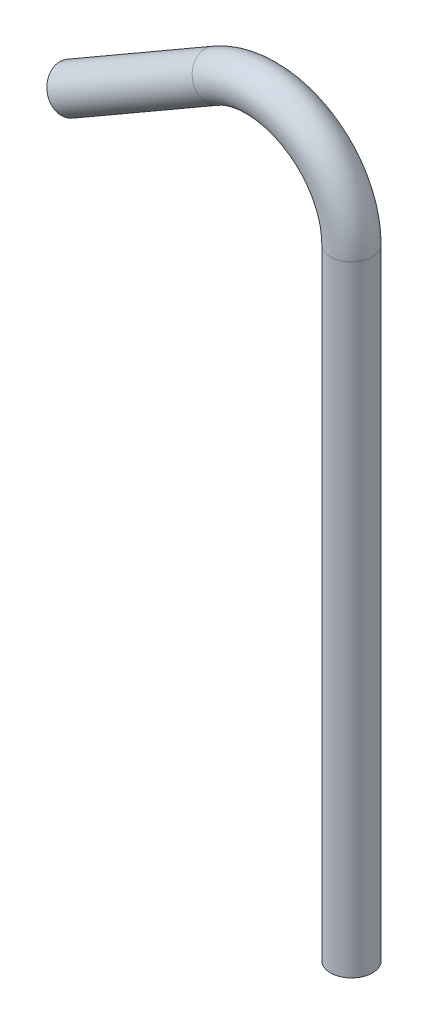
SolidWorks part; units mm, degrees
ref_plane "Front Plane" through (0, 0, 0) normal (0, 0, 1) x (1, 0, 0)
ref_plane "Top Plane" through (0, 0, 0) normal (0, 1, 0) x (1, 0, 0)
ref_plane "Right Plane" through (0, 0, 0) normal (1, 0, 0) x (0, 0, -1)
ref_axis "Axis1" through (0, 116.3153, 0) along (0, -1, 0)
sketch "Sketch1" plane through (0, 0, 0) normal (0, 1, 0) x (1, 0, 0)
  circle A0 centre (0, 0) radius 3.175
  circle A1 centre (0, 0) radius 2.16
  dimension "D1" = 6.35
  dimension "D2" = 4.32
sketch "Sketch2" plane through (0, 0, 0) normal (0, 0, 1) x (1, 0, 0)
  line L0 (-42.571, 93.062) -> (-20.574, 105.762)
  line L1 (0, -3.4925) -> (0, 3.4925) construction
  line L2 (0, 116.3153) -> (0, -5.5388) construction
  line L3 (0, 93.8836) -> (0, 0)
  arc A0 (-20.574, 105.762) -> (0, 93.8836) centre (-13.716, 93.8836) cw
  dimension "D2" = 13.716
  dimension "D1" = 60
  dimension "D3" = 25.4
  dimension "D4" = 93.8836
sweep "Sweep1" add profiles "Sketch1" path "Sketch2"
